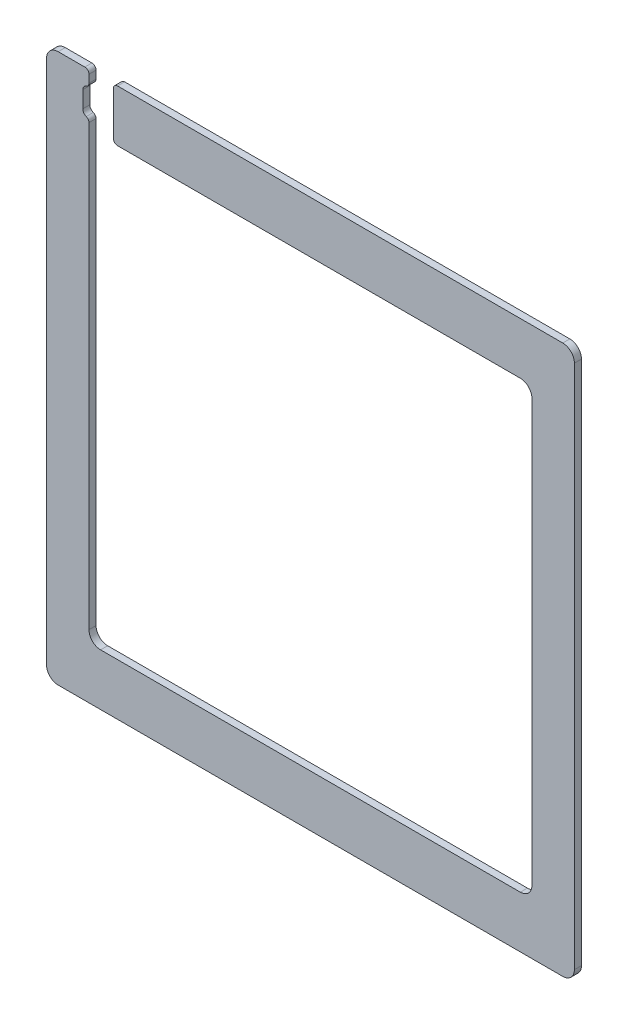
SolidWorks part; units mm, degrees
ref_plane "Front Plane" through (0, 0, 0) normal (0, 0, 1) x (1, 0, 0)
ref_plane "Top Plane" through (0, 0, 0) normal (0, 1, 0) x (1, 0, 0)
ref_plane "Right Plane" through (0, 0, 0) normal (1, 0, 0) x (0, 0, -1)
sketch "Sketch1" plane through (0, 0, 0) normal (0, 0, 1) x (1, 0, 0)
  line L1 (-161.925, -168.275) -> (161.925, -168.275)
  line L2 (-161.925, -168.275) -> (-161.925, 168.275)
  line L3 (-161.925, 168.275) -> (161.925, 168.275)
  line L4 (161.925, -168.275) -> (161.925, 168.275)
  line L5 (-161.925, -168.275) -> (161.925, 168.275) construction
  line L6 (-161.925, 168.275) -> (161.925, -168.275) construction
  point P0 (0, 0)
  dimension "D1" = 323.85
  dimension "D2" = 336.55
extrude "Boss-Extrude1" add sketch "Sketch1" along normal blind 4.3434
sketch "Sketch2" plane through (0, 0, 4.3434) normal (0, 0, 1) x (1, 0, 0)
  line L1 (-135.89, -136.525) -> (135.89, -136.525)
  line L2 (-135.89, -136.525) -> (-135.89, 136.525)
  line L3 (-135.89, 136.525) -> (135.89, 136.525)
  line L4 (135.89, -136.525) -> (135.89, 136.525)
  line L5 (-135.89, -136.525) -> (135.89, 136.525) construction
  line L6 (-135.89, 136.525) -> (135.89, -136.525) construction
  point P0 (0, 0)
  dimension "D1" = 271.78
  dimension "D2" = 273.05
extrude "Cut-Extrude1" cut sketch "Sketch2" against normal through all
fillet "Fillet1" radius 7.1437 8 edges at (135.89, -136.525, 2.1717) (135.89, 136.525, 2.1717) (-135.89, 136.525, 2.1717) (-135.89, -136.525, 2.1717) (-161.925, -168.275, 2.1717) (161.925, -168.275, 2.1717) (161.925, 168.275, 2.1717) (-161.925, 168.275, 2.1717)
sketch "Sketch3" plane through (0, 0, 4.3434) normal (0, 0, 1) x (1, 0, 0)
  line L0 (-136.525, 145.415) -> (-136.525, 155.575) construction
  line L1 (-139.7, 145.415) -> (-139.7, 155.575)
  line L2 (-133.35, 145.415) -> (-133.35, 155.575)
  line L3 (-161.925, 161.1312) -> (-161.925, -161.1313) construction
  line L5 (154.7812, 168.275) -> (-154.7812, 168.275) construction
  arc A0 (-139.7, 145.415) -> (-133.35, 145.415) centre (-136.525, 145.415) ccw
  arc A1 (-133.35, 155.575) -> (-139.7, 155.575) centre (-136.525, 155.575) ccw
  point P2 (-136.525, 150.495)
  dimension "D1" = 6.35
  dimension "D2" = 25.4
  dimension "D3" = 22.86
  dimension "D4" = 12.7
extrude "Cut-Extrude2" cut sketch "Sketch3" against normal through all
sketch "Sketch4" plane through (0, 0, 4.3434) normal (0, 0, 1) x (1, 0, 0)
  line L0 (-135.89, 168.275) -> (-120.9103, 168.275)
  line L1 (-135.89, 168.275) -> (-135.89, 121.3499)
  line L2 (-120.9103, 168.275) -> (-120.9103, 121.3499)
  line L3 (-135.89, 121.3499) -> (-120.9103, 121.3499)
  line L4 (154.7812, 168.275) -> (-154.7812, 168.275) construction
  line L5 (-135.89, 129.3812) -> (-135.89, -129.3812) construction
extrude "Cut-Extrude3" cut sketch "Sketch4" against normal through all
fillet "Fillet2" radius 2.54 5 edges at (-135.89, 168.275, 2.1717) (-120.9103, 168.275, 2.1717) (-120.9103, 136.525, 2.1717) (-135.89, 142.3041, 2.1717) (-135.89, 158.6859, 2.1717)
